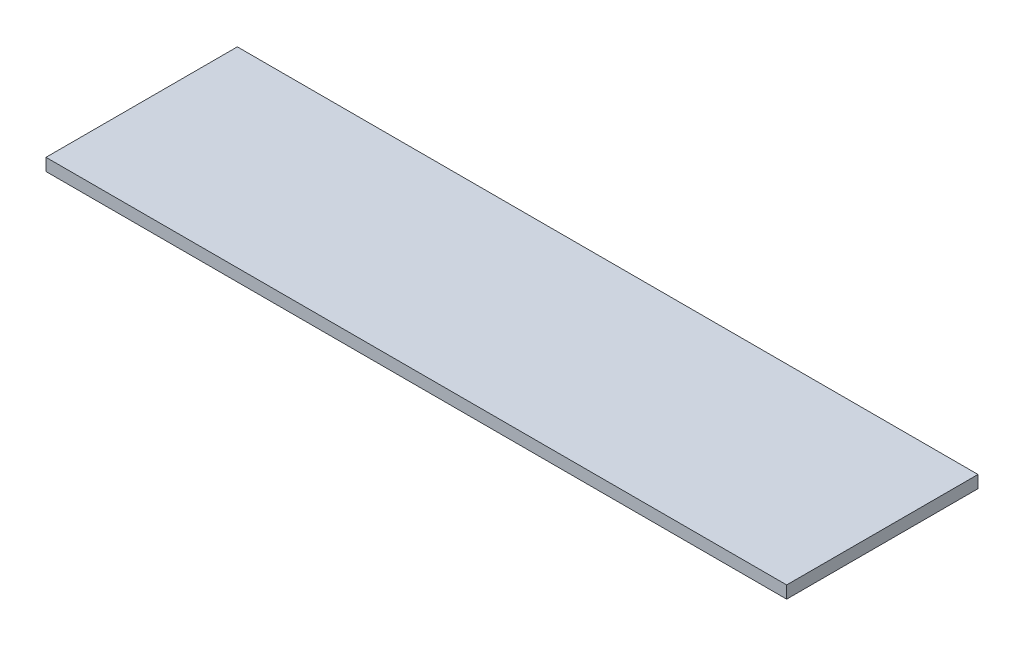
SolidWorks part; units mm, degrees
ref_plane "Plan de face" through (0, 0, 0) normal (0, 0, 1) x (1, 0, 0)
ref_plane "Plan de dessus" through (0, 0, 0) normal (0, 1, 0) x (1, 0, 0)
ref_plane "Plan de droite" through (0, 0, 0) normal (1, 0, 0) x (0, 0, -1)
sketch "Esquisse1" plane through (0, 0, 0) normal (0, 1, 0) x (1, 0, 0)
  line L1 (0, 0) -> (600, 0)
  line L2 (0, 0) -> (0, 155)
  line L3 (0, 155) -> (600, 155)
  line L4 (600, 0) -> (600, 155)
  dimension "D1" = 600
  dimension "D2" = 155
extrude "Boss.-Extru.1" add sketch "Esquisse1" along normal blind 10
